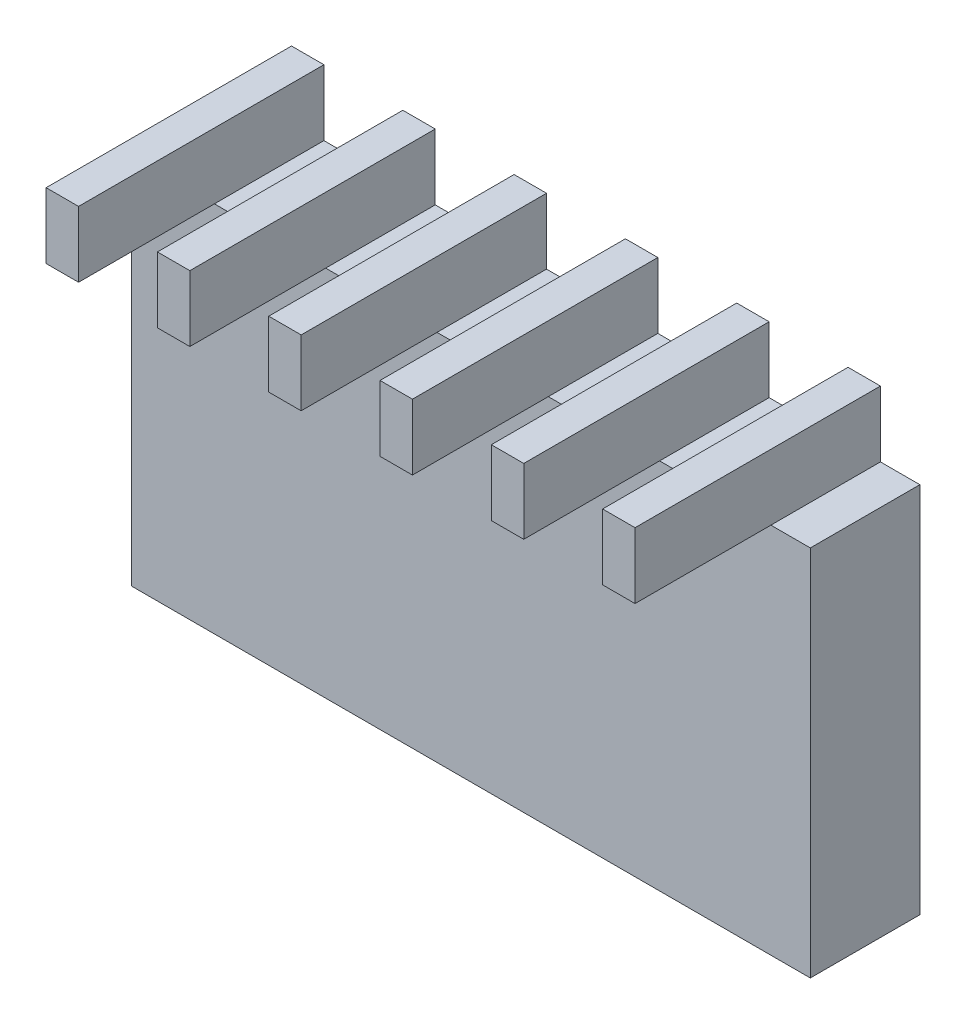
SolidWorks part; units mm, degrees
ref_plane "前视基准面" through (0, 0, 0) normal (0, 0, 1) x (1, 0, 0)
ref_plane "上视基准面" through (0, 0, 0) normal (0, 1, 0) x (1, 0, 0)
ref_plane "右视基准面" through (0, 0, 0) normal (1, 0, 0) x (0, 0, -1)
other "Configuration Table"
sketch "草图1" plane through (0, 0, 0) normal (0, 0, 1) x (1, 0, 0)
  line L0 (7.3822, -4.2023) -> (7.3822, 4.2977) construction
  line L1 (-5.5678, 4.2977) -> (20.3322, 4.2977)
  line L2 (-5.5678, 4.2977) -> (-5.5678, -4.2023)
  line L3 (-5.5678, -4.2023) -> (20.3322, -4.2023)
  line L4 (20.3322, 4.2977) -> (20.3322, -4.2023)
  line L5 (-4.4178, 5.7977) -> (19.1822, 5.7977)
  line L6 (-4.4178, 5.7977) -> (-4.4178, 4.2977)
  line L7 (-4.4178, 4.2977) -> (19.1822, 4.2977)
  line L8 (19.1822, 5.7977) -> (19.1822, 4.2977)
  dimension "D1" = 8.5
  dimension "D2" = 25.9
  dimension "D3" = 23.6
  dimension "D4" = 10
  dimension "D5" = 1.15
extrude "凸台-拉伸1" add sketch "草图1" along normal blind 2.5 contours L3 L4 L1 L2
extrude "凸台-拉伸2" add sketch "草图1<5>" along normal blind 2.5 contours L5 L8 L7 L6
sketch "草图1<5>" plane through (0, 0, 0) normal (0, 0, 1) x (1, 0, 0) same geometry as "草图1"
sketch "草图2" plane through (0, 0, 2.5) normal (0, 0, 1) x (1, 0, 0)
  line L0 (-4.4178, 4.2977) -> (19.1822, 4.2977)
  line L1 (-4.4178, 5.7977) -> (-4.4178, 4.2977) construction
  line L2 (-4.4178, 5.7977) -> (19.1822, 5.7977) construction
  line L3 (19.1822, 5.7977) -> (19.1822, 4.2977) construction
  line L4 (19.1822, 5.7977) -> (19.1822, 4.2977)
  line L5 (-4.4178, 5.7977) -> (19.1822, 5.7977)
  line L6 (-4.4178, 5.7977) -> (-4.4178, 4.2977)
extrude "凸台-拉伸3" add sketch "草图2" along normal blind 3.1
sketch "草图3" plane through (0, 5.7977, 0) normal (0, 1, 0) x (1, 0, 0)
  line L0 (19.1822, -5.6) -> (-4.4178, -5.6) construction
  line L1 (16.6422, 0) -> (18.4422, 0)
  line L2 (16.6422, 0) -> (16.6422, -5.6)
  line L3 (16.6422, -5.6) -> (18.4422, -5.6)
  line L4 (18.4422, 0) -> (18.4422, -5.6)
  line L5 (19.1822, -5.6) -> (19.1822, 0) construction
  line L6 (14.1022, 0) -> (14.1022, -5.6)
  line L7 (14.1022, 0) -> (15.9022, 0)
  line L8 (15.9022, 0) -> (15.9022, -5.6)
  line L9 (14.1022, -5.6) -> (15.9022, -5.6)
  line L10 (11.5622, 0) -> (11.5622, -5.6)
  line L11 (11.5622, 0) -> (13.3622, 0)
  line L12 (13.3622, 0) -> (13.3622, -5.6)
  line L13 (11.5622, -5.6) -> (13.3622, -5.6)
  line L14 (9.0222, 0) -> (9.0222, -5.6)
  line L15 (9.0222, 0) -> (10.8222, 0)
  line L16 (10.8222, 0) -> (10.8222, -5.6)
  line L17 (9.0222, -5.6) -> (10.8222, -5.6)
  line L18 (6.4822, 0) -> (6.4822, -5.6)
  line L19 (6.4822, 0) -> (8.2822, 0)
  line L20 (8.2822, 0) -> (8.2822, -5.6)
  line L21 (6.4822, -5.6) -> (8.2822, -5.6)
  line L22 (3.9422, 0) -> (3.9422, -5.6)
  line L23 (3.9422, 0) -> (5.7422, 0)
  line L24 (5.7422, 0) -> (5.7422, -5.6)
  line L25 (3.9422, -5.6) -> (5.7422, -5.6)
  line L26 (1.4022, 0) -> (1.4022, -5.6)
  line L27 (1.4022, 0) -> (3.2022, 0)
  line L28 (3.2022, 0) -> (3.2022, -5.6)
  line L29 (1.4022, -5.6) -> (3.2022, -5.6)
  line L30 (-1.1378, 0) -> (-1.1378, -5.6)
  line L31 (-1.1378, 0) -> (0.6622, 0)
  line L32 (0.6622, 0) -> (0.6622, -5.6)
  line L33 (-1.1378, -5.6) -> (0.6622, -5.6)
  line L34 (-3.6778, 0) -> (-3.6778, -5.6)
  line L35 (-3.6778, 0) -> (-1.8778, 0)
  line L36 (-1.8778, 0) -> (-1.8778, -5.6)
  line L37 (-3.6778, -5.6) -> (-1.8778, -5.6)
  line L38 (-4.4178, 0) -> (19.1822, 0) construction
  point P8 (-4.0478, 0)
  dimension "D1" = 1.8
  dimension "D2" = 0.74
  dimension "D4" = 0.37
  dimension "D3" = 9
extrude "切除-拉伸1" cut sketch "草图3" against normal blind 1.5
sketch "草图4" plane through (0, 4.2977, 0) normal (0, 1, 0) x (1, 0, 0)
  line L1 (9.9222, 1.4866) -> (24.9222, 1.4866)
  line L2 (9.9222, 1.4866) -> (9.9222, -6.2433)
  line L3 (9.9222, -6.2433) -> (24.9222, -6.2433)
  line L4 (24.9222, 1.4866) -> (24.9222, -6.2433)
  line L5 (10.8222, -5.6) -> (10.8222, 0) construction
  dimension "D1" = 0.9
  dimension "D2" = 15
extrude "切除-拉伸2" cut sketch "草图4" against normal blind 10 and the other way blind 2
sketch "草图5" plane through (0, 0, 0) normal (0, 0, -1) x (-1, 0, 0)
  line L0 (4.0478, 5.7977) -> (4.0478, -4.2023) construction
  line L3 (5.5678, 4.2977) -> (5.5678, -4.2023) construction
  dimension "D1" = 1.52
sketch "草图6" plane through (0, -4.2023, 0) normal (0, -1, 0) x (1, 0, 0)
  line L0 (-4.0478, 2.5) -> (-4.0478, 0)
  line L1 (-4.4178, 2.5) -> (-3.6778, 2.5) construction
sketch "草图7" plane through (0, -4.2023, 0) normal (0, -1, 0) x (1, 0, 0)
  line L6 (-5.5678, 1.25) -> (1.4206, 1.25) construction
  line L8 (-4.0478, 2.5) -> (-4.0478, 0) construction
  line L9 (-4.8723, 1.9913) -> (-3.2233, 1.9913)
  line L10 (-4.8723, 1.9913) -> (-4.8723, 0.5087)
  line L11 (-4.8723, 0.5087) -> (-3.2233, 0.5087)
  line L12 (-3.2233, 1.9913) -> (-3.2233, 0.5087)
  line L13 (-4.8723, 1.9913) -> (-3.2233, 0.5087) construction
  line L14 (-4.8723, 0.5087) -> (-3.2233, 1.9913) construction
  point P0 (-4.0478, 1.25)
sketch "草图9" plane through (0, 5.7977, 0) normal (0, 1, 0) x (1, 0, 0)
  line L0 (-4.0478, -5.6) -> (-4.0478, -2.5)
  line L1 (-3.6778, -5.6) -> (-4.4178, -5.6) construction
